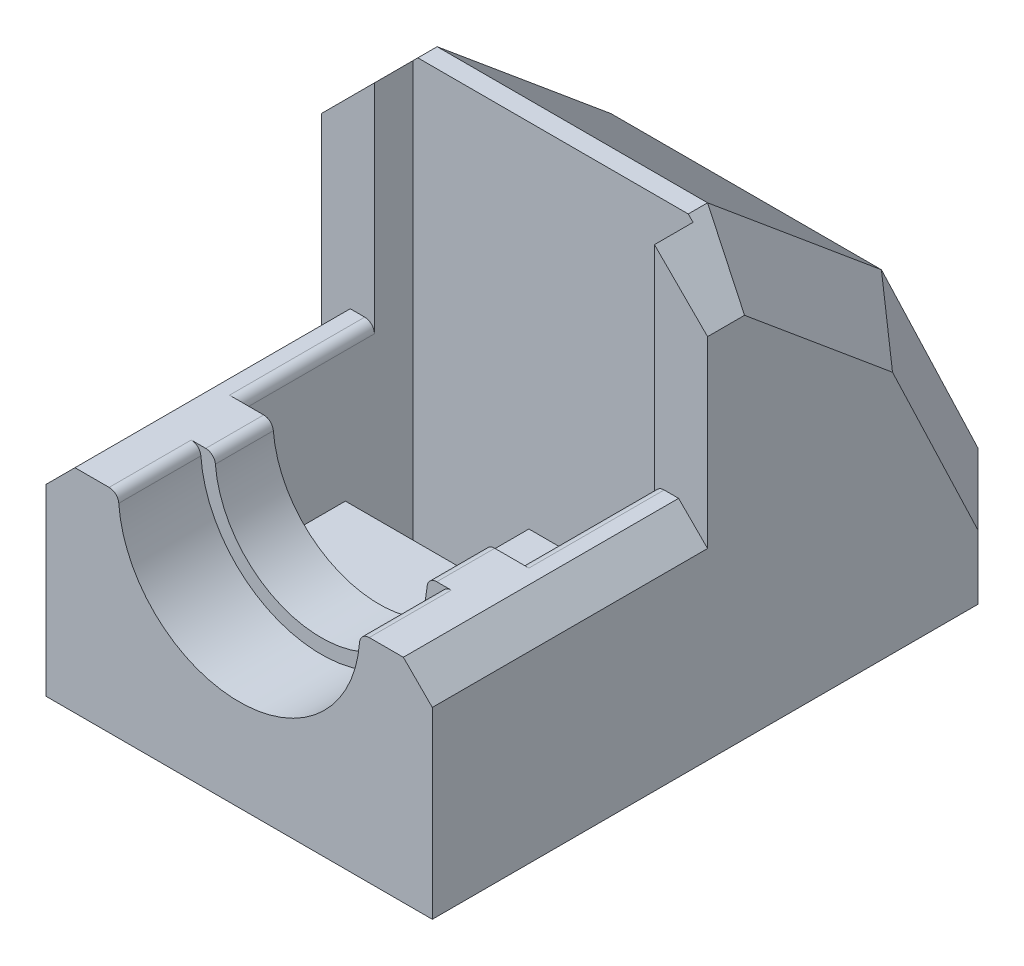
SolidWorks part; units mm, degrees
ref_plane "Ebene vorne" through (0, 0, 0) normal (0, 0, 1) x (1, 0, 0)
ref_plane "Ebene oben" through (0, 0, 0) normal (0, 1, 0) x (1, 0, 0)
ref_plane "Ebene rechts" through (0, 0, 0) normal (1, 0, 0) x (0, 0, -1)
sketch "Skizze1" plane through (0, 0, 0) normal (0, 0, 1) x (1, 0, 0)
  line L1 (0, 0) -> (20, 0)
  line L2 (0, 0) -> (0, 22)
  line L3 (0, 22) -> (20, 22)
  line L4 (20, 0) -> (20, 22)
  dimension "D1" = 22
  dimension "D2" = 20
extrude "Aufsatz-Linear austragen1" add sketch "Skizze1" along normal blind 35
sketch "Skizze2" plane through (0, 0, 35) normal (0, 0, 1) x (1, 0, 0)
  line L0 (0, 22) -> (0, 0) construction
  line L1 (20, 22) -> (0, 22) construction
  circle A0 centre (10, 11) radius 5.5
  dimension "D3" = 11
  dimension "D1" = 10
  dimension "D2" = 11
extrude "Schnitt-Linear austragen1" cut sketch "Skizze2" against normal blind 11
sketch "Skizze3" plane through (0, 0, 35) normal (0, 0, 1) x (1, 0, 0)
  line L0 (20, 0) -> (20, 22) construction
  line L1 (20, 22) -> (0, 22) construction
  circle A0 centre (10, 11) radius 6.25
  dimension "D1" = 10
  dimension "D2" = 11
extrude "Schnitt-Linear austragen2" cut sketch "Skizze3" against normal blind 8
sketch "Skizze5" plane through (0, 0, 24) normal (0, 0, 1) x (1, 0, 0)
  line L0 (0, 22) -> (0, 0) construction
  line L1 (2.75, 3.75) -> (17.25, 3.75)
  line L2 (2.75, 3.75) -> (2.75, 22)
  line L3 (2.75, 22) -> (17.25, 22)
  line L4 (17.25, 3.75) -> (17.25, 22)
  line L6 (0, 0) -> (20, 0) construction
  dimension "D1" = 18.25
  dimension "D2" = 14.5
  dimension "D3" = 2.75
  dimension "D4" = 3.75
extrude "Schnitt-Linear austragen3" cut sketch "Skizze5" against normal blind 9
sketch "Skizze13" plane through (0, 0, 35) normal (0, 0, 1) x (1, 0, 0)
  line L0 (20, 0) -> (20, 22) construction
  line L1 (0, 22) -> (20, 22)
  line L2 (0, 22) -> (0, 11)
  line L3 (0, 11) -> (20, 11)
  line L4 (20, 22) -> (20, 11)
extrude "Schnitt-Linear austragen6" cut sketch "Skizze13" against normal blind 18
sketch "Skizze16" plane through (0, 0, 0) normal (-1, 0, 0) x (0, 0, 1)
  line L0 (14, 22) -> (5, 14.5)
  line L1 (17, 22) -> (0, 22) construction
  line L2 (5, 14.5) -> (0, 4)
  line L3 (0, 22) -> (0, 0) construction
  line L4 (0, 4) -> (0, 22)
  line L5 (0, 22) -> (14, 22)
  line L6 (17, 22) -> (17, 11) construction
  dimension "D1" = 3
  dimension "D2" = 5
  dimension "D3" = 18
  dimension "D4" = 10.5
extrude "Schnitt-Linear austragen7" cut sketch "Skizze16" against normal through all
fillet "Verrundung1" radius 0.5 6 edges at (16.25, 11, 31) (3.75, 11, 31) (4.5, 11, 25.5) (15.5, 11, 25.5) (17.25, 11, 20.5) (2.75, 11, 20.5)
chamfer "Fase1" distance 3 angle 45 2 edges at (20, 22, 15.5) (0, 22, 15.5)
chamfer "Fase2" distance 3 angle 45 2 edges at (0, 16.75, 7.7) (20, 16.75, 7.7)
chamfer "Fase3" distance 3 angle 45 4 edges at (20, 6.0129, 0.9585) (20, 2, 0) (0, 6.0129, 0.9585) (0, 2, 0)
chamfer "Fase4" distance 1.5 angle 45 2 edges at (20, 11, 26) (0, 11, 26)
sketch "Skizze17" plane through (0, 3.75, 0) normal (0, 1, 0) x (1, 0, 0)
  line L1 (2.75, -15) -> (8.75, -15)
  line L2 (2.75, -15) -> (2.75, -18.5)
  line L3 (2.75, -18.5) -> (8.75, -18.5)
  line L4 (8.75, -15) -> (8.75, -18.5)
  dimension "D1" = 6
  dimension "D2" = 3.5
extrude "Schnitt-Linear austragen8" cut sketch "Skizze17" against normal through all
sketch "Skizze18" plane through (0, 0, 0) normal (-1, 0, 0) x (0, 0, 1)
  line L0 (17, 11) -> (35, 11) construction
  line L1 (35, 0) -> (31.25, 0)
  line L2 (35, 0) -> (35, 11)
  line L3 (35, 11) -> (31.25, 11)
  line L4 (31.25, 0) -> (31.25, 11)
  dimension "D1" = 3.75
extrude "Schnitt-Linear austragen9" cut sketch "Skizze18" against normal up to surface (20 mm away) up to face at (20, 9.1173, 16.564)
